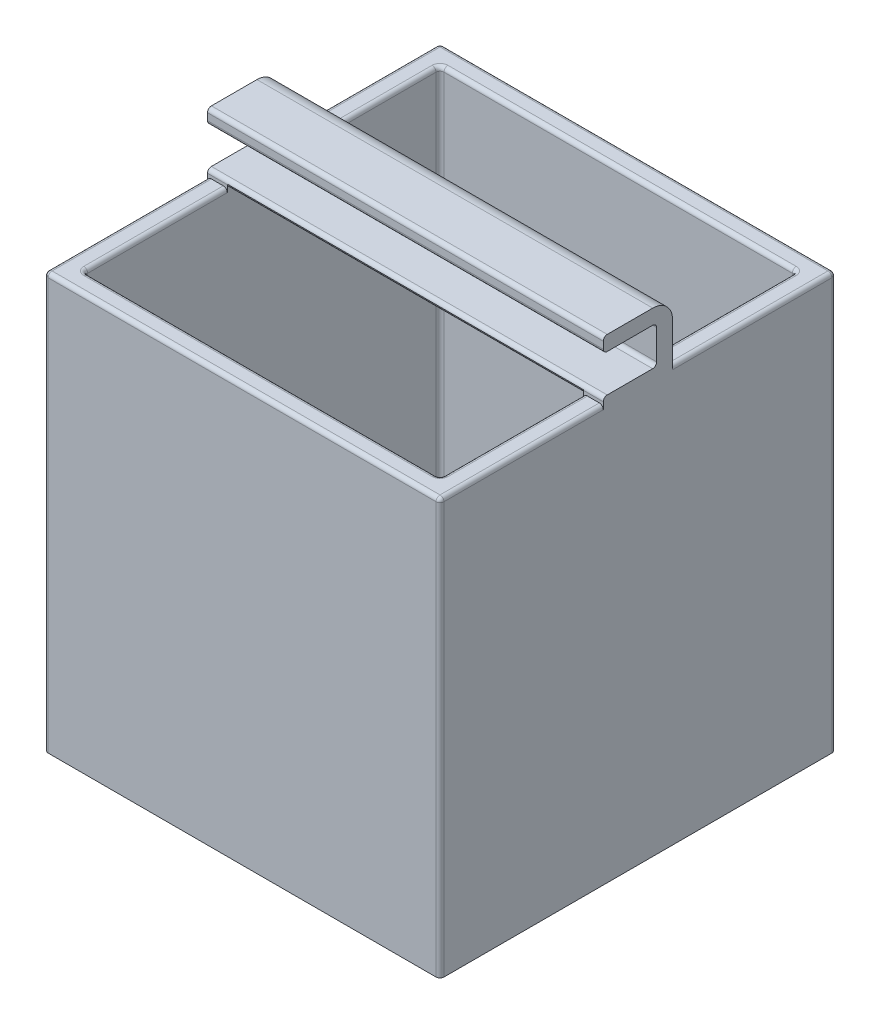
SolidWorks part; units mm, degrees
ref_plane "Front Plane" through (0, 0, 0) normal (0, 0, 1) x (1, 0, 0)
ref_plane "Top Plane" through (0, 0, 0) normal (0, 1, 0) x (1, 0, 0)
ref_plane "Right Plane" through (0, 0, 0) normal (1, 0, 0) x (0, 0, -1)
sketch "Sketch1" plane through (0, 0, 0) normal (0, 1, 0) x (1, 0, 0)
  line L1 (-100, -100) -> (100, -100)
  line L2 (-100, -100) -> (-100, 100)
  line L3 (-100, 100) -> (100, 100)
  line L4 (100, -100) -> (100, 100)
  line L5 (-100, -100) -> (100, 100) construction
  line L6 (-100, 100) -> (100, -100) construction
  line L7 (-90, -90) -> (90, -90)
  line L8 (-90, -90) -> (-90, 90)
  line L9 (-90, 90) -> (90, 90)
  line L10 (90, -90) -> (90, 90)
  line L11 (-90, -90) -> (90, 90) construction
  line L12 (-90, 90) -> (90, -90) construction
  point P0 (0, 0)
  point P6 (0, 0)
  dimension "D1" = 200
  dimension "D2" = 200
  dimension "D3" = 10
extrude "Boss-Extrude1" add sketch "Sketch1" along normal blind 200
sketch "Sketch2" plane through (0, 0, 0) normal (0, -1, 0) x (1, 0, 0)
  line L1 (-100, 100) -> (100, 100)
  line L2 (-100, 100) -> (-100, -100)
  line L3 (-100, -100) -> (100, -100)
  line L4 (100, 100) -> (100, -100)
extrude "Boss-Extrude2" add sketch "Sketch2" along normal blind 10
sketch "Sketch3" plane through (0, 200, 0) normal (0, 1, 0) x (1, 0, 0)
  line L0 (0, 0) -> (100, 0) construction
  line L1 (100, -100) -> (100, 100) construction
  line L2 (-100, 100) -> (-100, -100) construction
  line L3 (100, 17.5) -> (-100, 17.5)
  line L4 (100, 17.5) -> (100, -17.5)
  line L5 (100, -17.5) -> (-100, -17.5)
  line L6 (-100, 17.5) -> (-100, -17.5)
  line L7 (100, 17.5) -> (-100, -17.5) construction
  line L8 (100, -17.5) -> (-100, 17.5) construction
  dimension "D1" = 35
extrude "Boss-Extrude3" add sketch "Sketch3" along normal blind 30
sketch "Sketch4" plane through (100, 0, 0) normal (1, 0, 0) x (0, 0, -1)
  line L0 (-17.5, 230) -> (-17.5, 200) construction
  line L1 (-17.5, 222.4972) -> (9.4548, 222.4972)
  line L2 (-17.5, 222.4972) -> (-17.5, 203.4972)
  line L3 (-17.5, 203.4972) -> (9.4548, 203.4972)
  line L4 (9.4548, 222.4972) -> (9.4548, 203.4972)
  dimension "D1" = 19
extrude "Cut-Extrude1" cut sketch "Sketch4" against normal through all both and the other way through all
fillet "Fillet1" radius 10 1 edges at (0, 230, -17.5)
fillet "Fillet3" radius 2 1 edges at (0, 200, -17.5)
fillet "Fillet4" radius 2 23 edges at (90, 200, -53.75) (0, 200, -90) (-90, 200, 53.75) (90, 200, 53.75) (-90, 200, -53.75) (0, 200, 90) (-90, 100, 90) (90, 100, 90) (-90, 0, 0) (-90, 100, -90) (90, 100, -90) (0, 0, -90) (90, 0, 0) (100, 200, -58.75) (100, 200, 58.75) (-100, 200, 58.75) (-100, 200, -58.75) (0, 200, 100) (100, 95, 100) (-100, 95, 100) (0, 200, -100) (-100, 95, -100) (100, 95, -100)
fillet "Fillet6" radius 2 1 edges at (0, 200, 17.5)
fillet "Fillet7" radius 2 1 edges at (0, 203.4972, -9.4548)
fillet "Fillet8" radius 2 3 edges at (0, 230, 17.5) (0, 222.4972, 17.5) (0, 222.4972, -9.4548)
fillet "Fillet9" radius 2 1 edges at (0, 203.4972, 17.5)
